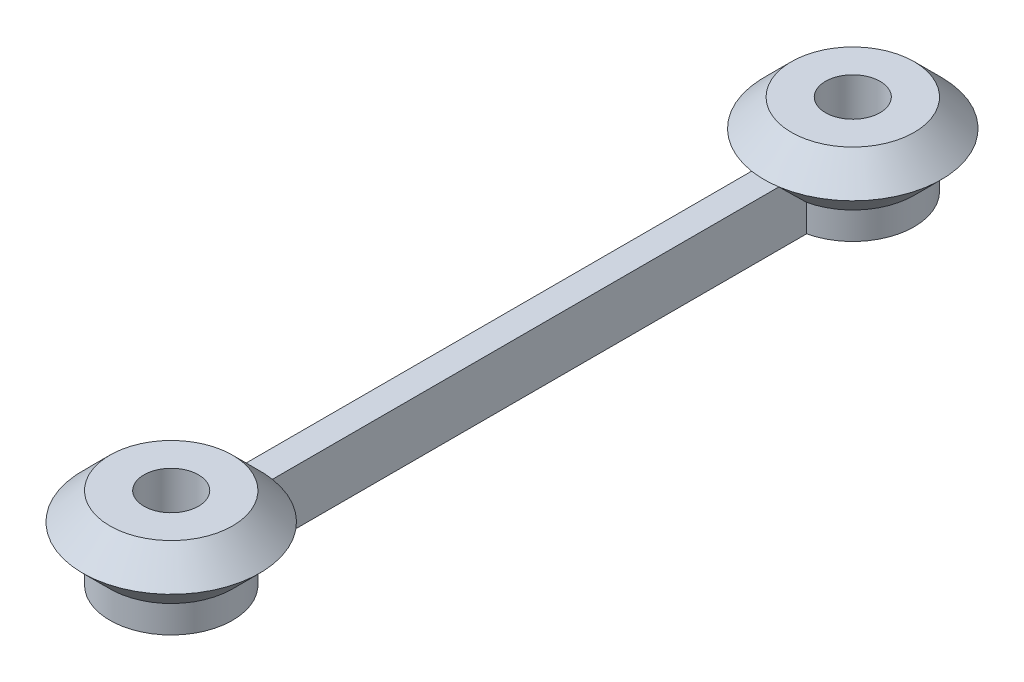
SolidWorks part; units mm, degrees
ref_plane "Front Plane" through (0, 0, 0) normal (0, 0, 1) x (1, 0, 0)
ref_plane "Top Plane" through (0, 0, 0) normal (0, 1, 0) x (1, 0, 0)
ref_plane "Right Plane" through (0, 0, 0) normal (1, 0, 0) x (0, 0, -1)
ref_axis "Axis1" through (0, 55, 0) along (0, -1, 0)
sketch "Sketch1" plane through (0, 0, 0) normal (1, 0, 0) x (0, 0, -1)
  line L0 (1.5, 0) -> (1.5, 5)
  line L1 (1.5, 5) -> (4, 5)
  line L2 (4, 5) -> (4, 12)
  line L3 (4, 12) -> (9, 12)
  line L4 (9, 12) -> (13, 8)
  line L6 (9, 0) -> (1.5, 0)
  line L7 (0, 55) -> (0, -55) construction
  line L8 (9, 0) -> (9, 4)
  line L9 (9, 4) -> (13, 8)
  point P9 (11.2308, 3.145)
  point P11 (9, 3.145)
  point P12 (0, 0)
  point P13 (0, 0)
  dimension "D1" = 4
  dimension "D2" = 1.5
  dimension "D3" = 4
  dimension "D4" = 5
  dimension "D5" = 12
  dimension "D6" = 5
  dimension "D7" = 4
revolve "Revolve1" add sketch "Sketch1" angle 360 about axis through (0, 55, 0) along (0, -1, 0)
ref_plane "Plane1" through (0, 0, -50) normal (0, 0, 1) x (1, 0, 0)
mirror "Mirror2" about plane through (0, 0, -50) normal (0, 0, 1) of bodies 101
sketch "Sketch2" plane through (0, 0, 0) normal (0, 1, 0) x (1, 0, 0)
  line L0 (-39.6, 50) -> (39.6, 50) construction
  line L1 (-2, 4) -> (2, 4)
  line L2 (-2, 4) -> (-2, 96)
  line L3 (-2, 96) -> (2, 96)
  line L4 (2, 4) -> (2, 96)
  line L5 (0, 96) -> (0, 4) construction
  line L6 (-2, 50) -> (2, 50) construction
  point P0 (0, 50)
  point P6 (0, 0)
  dimension "D1" = 4
extrude "Boss-Extrude1" add sketch "Sketch2" along normal up to vertex (8 mm away) up to point (0, 8, -13)
